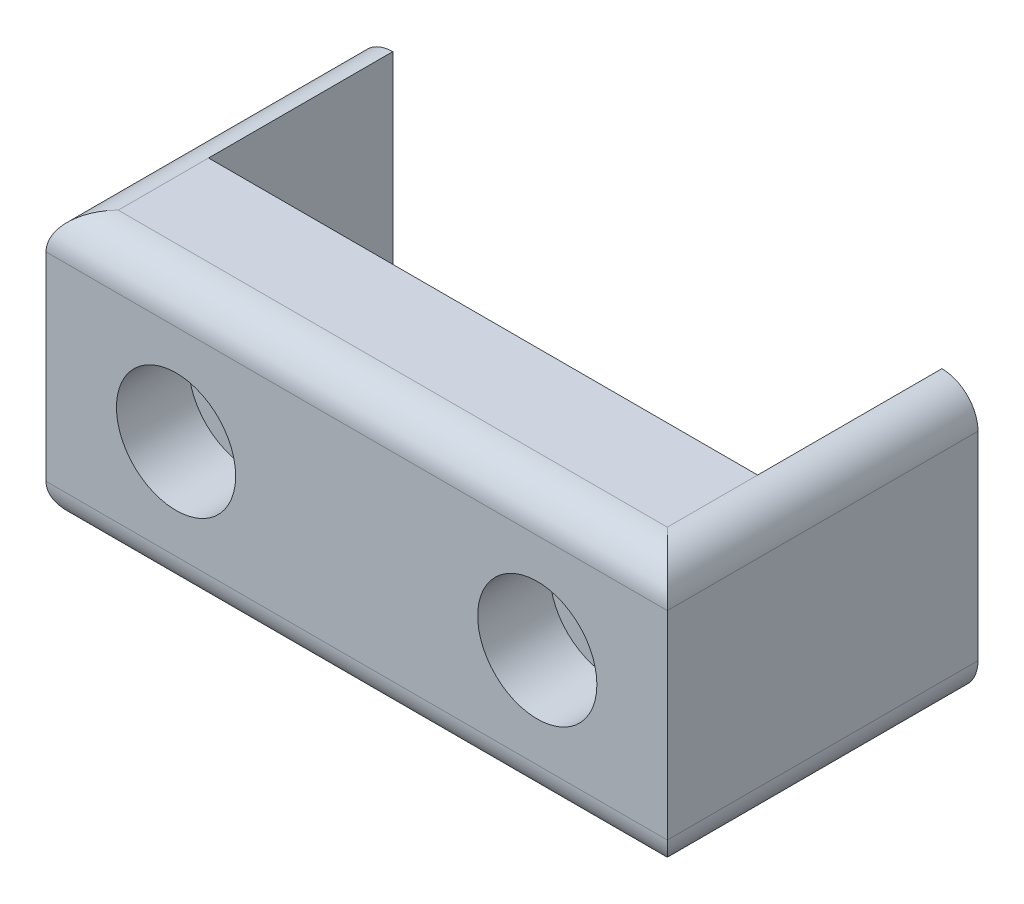
SolidWorks part; units mm, degrees
ref_plane "Front Plane" through (0, 0, 0) normal (0, 0, 1) x (1, 0, 0)
ref_plane "Top Plane" through (0, 0, 0) normal (0, 1, 0) x (1, 0, 0)
ref_plane "Right Plane" through (0, 0, 0) normal (1, 0, 0) x (0, 0, -1)
sketch "Sketch1" plane through (0, 0, 0) normal (0, 1, 0) x (1, 0, 0)
  line L0 (-21.844, 0) -> (21.844, 0)
  line L1 (-19.304, 12.954) -> (19.304, 12.954)
  line L2 (-19.304, 12.954) -> (-19.304, -12.954)
  line L3 (-19.304, -12.954) -> (19.304, -12.954)
  line L4 (19.304, 12.954) -> (19.304, -12.954)
  line L5 (-19.304, 12.954) -> (19.304, -12.954) construction
  line L6 (-19.304, -12.954) -> (19.304, 12.954) construction
  line L7 (-21.844, 21.844) -> (21.844, 21.844)
  line L8 (-21.844, 21.844) -> (-21.844, -21.844)
  line L9 (-21.844, -21.844) -> (21.844, -21.844)
  line L10 (21.844, 21.844) -> (21.844, -21.844)
  line L11 (-21.844, 21.844) -> (21.844, -21.844) construction
  line L12 (-21.844, -21.844) -> (21.844, 21.844) construction
  point P0 (0, 0)
  point P6 (0, 0)
  dimension "D1" = 38.608
  dimension "D2" = 25.908
  dimension "D3" = 43.688
  dimension "D4" = 43.688
extrude "Boss-Extrude1" add sketch "Sketch1" along normal blind 19.05 contours L10 L0 L4 L3 L2 L8 L9 region at (0, 0, 15.8166)
sketch "Sketch2" plane through (0, 0, 21.844) normal (0, 0, 1) x (1, 0, 0)
  line L0 (-21.844, 9.525) -> (21.844, 9.525) construction
  line L1 (-21.844, 19.05) -> (-21.844, 0) construction
  line L2 (21.844, 19.05) -> (21.844, 0) construction
  line L3 (-21.844, 0) -> (21.844, 0) construction
  circle A0 centre (-12.7, 9.525) radius 2.54
  circle A1 centre (12.7, 9.525) radius 2.54
  point P10 (0, 0)
  point P11 (0, 0)
  point P12 (0, 0)
  point P15 (0, 0)
  dimension "D1" = 5.08
  dimension "D2" = 5.08
  dimension "D3" = 12.7
  dimension "D4" = 12.7
extrude "Cut-Extrude1" cut sketch "Sketch2" against normal through all
sketch "Sketch3" plane through (0, 0, 21.844) normal (0, 0, 1) x (1, 0, 0)
  circle A0 centre (-12.7, 9.525) radius 4.191
  circle A1 centre (12.7, 9.525) radius 4.191
  circle A2 centre (-12.7, 9.525) radius 2.54 construction
  circle A3 centre (12.7, 9.525) radius 2.54 construction
  dimension "D1" = 8.382
  dimension "D2" = 8.382
extrude "Cut-Extrude2" cut sketch "Sketch3" against normal blind 5.08
fillet "Fillet1" radius 2.54 3 edges at (-21.844, 19.05, 10.922) (21.844, 19.05, 10.922) (0, 19.05, 21.844)
fillet "Fillet2" radius 2.54 3 edges at (-21.844, 0, 10.922) (0, 0, 21.844) (21.844, 0, 10.922)
